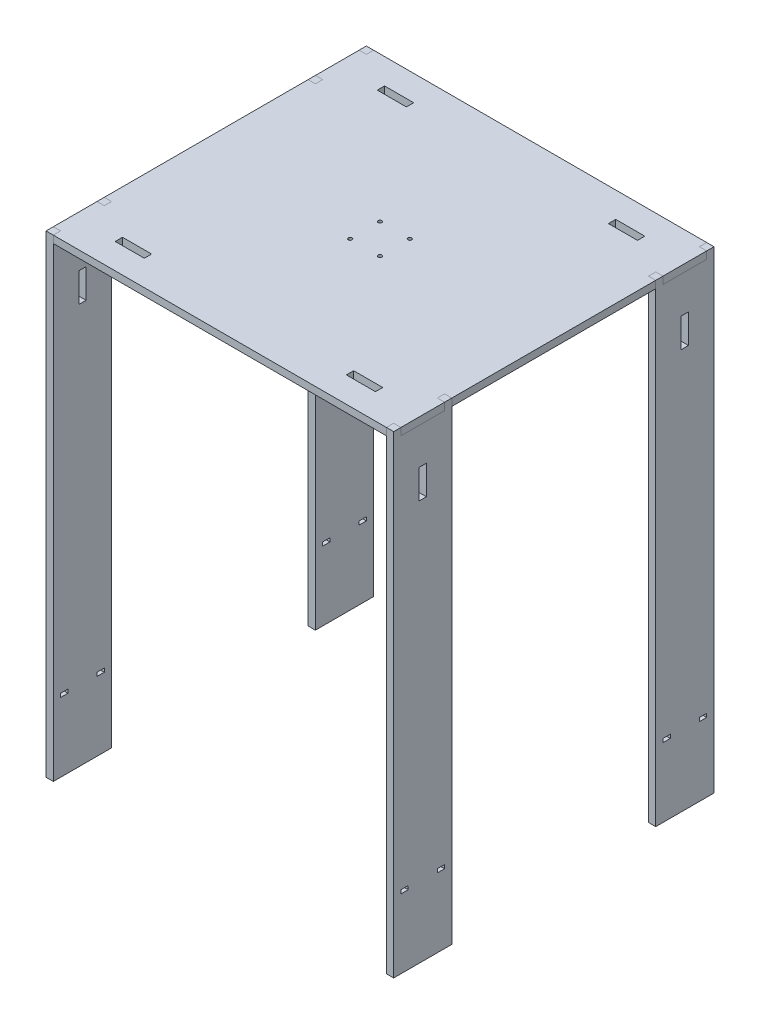
SolidWorks part; units mm, degrees
ref_plane "Front Plane" through (0, 0, 0) normal (0, 0, 1) x (1, 0, 0)
ref_plane "Top Plane" through (0, 0, 0) normal (0, 1, 0) x (1, 0, 0)
ref_plane "Right Plane" through (0, 0, 0) normal (1, 0, 0) x (0, 0, -1)
sketch "Sketch1" plane through (0, 0, 0) normal (0, 1, 0) x (1, 0, 0)
  line L0 (145.2562, 0) -> (-145.2562, 0) construction
  line L1 (-145.2562, 0) -> (-151.6062, 0) construction
  line L2 (0, 0) -> (0, 36.9734) construction
  line L3 (-145.2562, -25.4) -> (-151.6063, -25.4)
  line L4 (-145.2562, -25.4) -> (-145.2562, 25.4)
  line L5 (-145.2562, 25.4) -> (-151.6063, 25.4)
  line L6 (-151.6063, -25.4) -> (-151.6063, 25.4)
  line L7 (-145.2562, -25.4) -> (-151.6063, 25.4) construction
  line L8 (-145.2562, 25.4) -> (-151.6063, -25.4) construction
  line L9 (145.2562, 25.4) -> (151.6063, 25.4)
  line L10 (151.6063, -25.4) -> (151.6063, 25.4)
  line L11 (145.2562, -25.4) -> (151.6063, -25.4)
  line L12 (145.2562, -25.4) -> (145.2562, 25.4)
  point P0 (-148.4313, 0)
  point P4 (0, 0)
  dimension "D1" = 290.5125
  dimension "D2" = 6.35
  dimension "D3" = 50.8
extrude "Boss-Extrude1" add sketch "Sketch1" along normal blind 412.75
sketch "Sketch3" plane through (151.6063, 0, 0) normal (1, 0, 0) x (0, 0, -1)
  line L0 (0, 412.75) -> (0, 409.575) construction
  line L1 (-25.4, 412.75) -> (25.4, 412.75) construction
  line L2 (-25.4, 412.75) -> (-25.4, 0) construction
  line L3 (19.05, 406.4) -> (-19.05, 406.4)
  line L4 (19.05, 406.4) -> (19.05, 412.75)
  line L5 (19.05, 412.75) -> (-19.05, 412.75)
  line L6 (-19.05, 406.4) -> (-19.05, 412.75)
  line L7 (19.05, 406.4) -> (-19.05, 412.75) construction
  line L8 (19.05, 412.75) -> (-19.05, 406.4) construction
  line L9 (0, 406.4) -> (0, 63.5) construction
  line L10 (0, 63.5) -> (-19.05, 63.5) construction
  line L11 (19.05, 60.325) -> (12.7, 60.325)
  line L12 (-19.05, 63.5) -> (-12.7, 63.5)
  line L13 (-19.05, 63.5) -> (-19.05, 60.325)
  line L14 (-19.05, 60.325) -> (-12.7, 60.325)
  line L15 (-12.7, 63.5) -> (-12.7, 60.325)
  line L16 (12.7, 63.5) -> (12.7, 60.325)
  line L17 (19.05, 63.5) -> (12.7, 63.5)
  line L18 (19.05, 63.5) -> (19.05, 60.325)
  dimension "D1" = 3.175
  dimension "D2" = 6.35
  dimension "D3" = 342.9
  dimension "D4" = 6.35
  dimension "D5" = 6.35
  dimension "D6" = 3.175
extrude "Cut-Extrude1" cut sketch "Sketch3" against normal through all
sketch "Sketch4" plane through (0, 412.75, 0) normal (0, 1, 0) x (1, 0, 0)
  line L1 (-145.2562, 19.05) -> (-151.6063, 19.05)
  line L2 (-145.2562, 19.05) -> (-145.2562, -19.05)
  line L3 (-145.2562, -19.05) -> (-151.6063, -19.05)
  line L4 (-151.6063, 19.05) -> (-151.6063, -19.05)
  line L5 (151.6063, 19.05) -> (145.2562, 19.05)
  line L6 (151.6063, 19.05) -> (151.6063, -19.05)
  line L7 (151.6063, -19.05) -> (145.2562, -19.05)
  line L8 (145.2562, 19.05) -> (145.2562, -19.05)
  line L9 (145.2562, 25.4) -> (-145.2562, 25.4)
  line L10 (145.2562, 25.4) -> (145.2562, -25.4)
  line L11 (145.2562, -25.4) -> (-145.2562, -25.4)
  line L12 (-145.2562, 25.4) -> (-145.2562, -25.4)
  line M1 (-151.6063, 19.05) -> (-145.2562, 19.05)
  line M2 (-145.2562, 19.05) -> (-145.2562, 25.4)
extrude "Boss-Extrude2" add sketch "Sketch4" against normal blind 6.35 separate body contours L4 L3 L2 M1 | L2 L12 L11 L10 L8 L9 M2 | L5 L8 L7 L6 region at (-148.4313, 412.75, 0) region at (0, 412.75, 0) region at (148.4313, 412.75, 0)
sketch "Sketch5" plane through (0, 0, 0) normal (0, 1, 0) x (1, 0, 0)
  line L0 (151.6063, 25.4) -> (151.6063, 203.2) construction
  line L1 (151.6063, 114.3) -> (35.7143, 114.3) construction
  dimension "D1" = 177.8
ref_plane "Plane1" through (0, 0, -114.3) normal (0, 0, -1) x (-1, 0, 0)
mirror "Mirror6" about plane through (0, 0, -114.3) normal (0, 0, -1) of bodies 105 104 103
sketch "Sketch8" plane through (0, 412.75, 0) normal (0, 1, 0) x (1, 0, 0)
  line L1 (-151.6063, 203.2) -> (151.6063, 203.2)
  line L2 (-151.6063, 203.2) -> (-151.6063, 25.4)
  line L3 (-151.6063, 25.4) -> (151.6063, 25.4)
  line L4 (151.6063, 203.2) -> (151.6063, 25.4)
extrude "Boss-Extrude5" add sketch "Sketch8" against normal blind 6.35
sketch "Sketch9" plane through (0, 412.75, 0) normal (0, 1, 0) x (1, 0, 0)
  line L0 (-151.6063, 114.3) -> (151.6063, 114.3) construction
  line L1 (-151.6063, 203.2) -> (-151.6063, 25.4) construction
  line L2 (151.6063, 25.4) -> (151.6063, 203.2) construction
  line L3 (0, 254) -> (0, -25.4) construction
  line L4 (145.2562, 254) -> (-145.2562, 254) construction
  line L5 (145.2562, -25.4) -> (-145.2562, -25.4) construction
  line L6 (0, 254) -> (0, 228.6) construction
  line L7 (13, 101.3) -> (-13, 101.3) construction
  line L8 (13, 101.3) -> (13, 127.3) construction
  line L9 (13, 127.3) -> (-13, 127.3) construction
  line L10 (-13, 101.3) -> (-13, 127.3) construction
  line L11 (13, 101.3) -> (-13, 127.3) construction
  line L12 (13, 127.3) -> (-13, 101.3) construction
  line L13 (18.7789, 228.6) -> (-18.7789, 228.6) construction
  point P12 (0, 114.3)
  point P13 (0, 114.3)
  point P19 (-13, 127.3)
  point P20 (13, 127.3)
  point P21 (13, 101.3)
  point P22 (-13, 101.3)
  point P25 (0, 228.6)
  dimension "D1" = 26
  dimension "D2" = 25.4
hole_wizard "M3 Clearance Hole1" positions "Sketch10" profile "Sketch11" hole size "M3" standard "ANSI Metric" end condition through all
sketch "Sketch10" plane through (0, 412.75, 0) normal (0, 1, 0) x (1, 0, 0)
  point P0 (-13, 101.3)
  point P3 (-13, 127.3)
  point P6 (13, 127.3)
  point P9 (13, 101.3)
sketch "Sketch11" plane through (-13, 412.75, -101.3) normal (1, 0, 0) x (0, 0, 1)
  line L0 (0, 0) -> (0, 412.75)
  line L1 (0, 412.75) -> (1.6, 412.75)
  line L2 (1.6, 412.75) -> (1.6, 0)
  line L5 (1.6, 0) -> (0, 0)
  line L11 (0, -6.35) -> (0, 107.95) construction
  dimension "Thru Hole Dia." = 3.2
  dimension "Thru Hole Depth" = 412.75
sketch "Sketch12" plane through (0, 412.75, 0) normal (0, 1, 0) x (1, 0, 0)
  line L0 (-151.6063, 0) -> (-100.8063, 0) construction
  line L1 (-151.6063, 19.05) -> (-151.6063, -19.05) construction
  line L2 (0, -25.4) -> (0, 254) construction
  line L3 (-113.5063, -3.175) -> (-88.1063, -3.175)
  line L4 (-113.5063, -3.175) -> (-113.5063, 3.175)
  line L5 (-113.5063, 3.175) -> (-88.1063, 3.175)
  line L6 (-88.1063, -3.175) -> (-88.1063, 3.175)
  line L7 (-113.5063, -3.175) -> (-88.1063, 3.175) construction
  line L8 (-113.5063, 3.175) -> (-88.1063, -3.175) construction
  line L9 (145.2562, -25.4) -> (-145.2562, -25.4) construction
  line L10 (145.2562, 254) -> (-145.2562, 254) construction
  line L11 (-151.6063, 114.3) -> (151.6063, 114.3) construction
  line L12 (-151.6063, 203.2) -> (-151.6063, 25.4) construction
  line L13 (151.6063, 25.4) -> (151.6063, 203.2) construction
  line L14 (113.5063, 3.175) -> (88.1063, 3.175)
  line L15 (88.1063, -3.175) -> (88.1063, 3.175)
  line L16 (113.5063, -3.175) -> (88.1063, -3.175)
  line L17 (113.5063, -3.175) -> (113.5063, 3.175)
  line L18 (113.5063, 231.775) -> (113.5063, 225.425)
  line L19 (113.5063, 231.775) -> (88.1063, 231.775)
  line L20 (88.1063, 231.775) -> (88.1063, 225.425)
  line L21 (113.5063, 225.425) -> (88.1063, 225.425)
  line L22 (-113.5063, 225.425) -> (-88.1063, 225.425)
  line L23 (-88.1063, 231.775) -> (-88.1063, 225.425)
  line L24 (-113.5063, 231.775) -> (-88.1063, 231.775)
  line L25 (-113.5063, 231.775) -> (-113.5063, 225.425)
  dimension "D1" = 50.8
  dimension "D2" = 6.35
  dimension "D3" = 25.4
extrude "Cut-Extrude2" cut sketch "Sketch12" against normal up to next (6.35 mm away)
sketch "Sketch13" plane through (-151.6063, 0, 0) normal (-1, 0, 0) x (0, 0, 1)
  line L0 (-228.6, 412.75) -> (-228.6, 361.95) construction
  line L1 (-209.55, 412.75) -> (-247.65, 412.75) construction
  line L2 (-114.3, 412.75) -> (-114.3, 406.4)
  line L3 (-225.425, 349.25) -> (-231.775, 349.25)
  line L4 (-225.425, 349.25) -> (-225.425, 374.65)
  line L5 (-225.425, 374.65) -> (-231.775, 374.65)
  line L6 (-231.775, 349.25) -> (-231.775, 374.65)
  line L7 (-225.425, 349.25) -> (-231.775, 374.65) construction
  line L8 (-225.425, 374.65) -> (-231.775, 349.25) construction
  line L9 (-203.2, 412.75) -> (-25.4, 412.75) construction
  line L10 (-203.2, 406.4) -> (-25.4, 406.4) construction
  line L11 (-3.175, 374.65) -> (3.175, 374.65)
  line L12 (3.175, 349.25) -> (3.175, 374.65)
  line L13 (-3.175, 349.25) -> (3.175, 349.25)
  line L14 (-3.175, 349.25) -> (-3.175, 374.65)
  dimension "D1" = 6.35
  dimension "D2" = 25.4
  dimension "D3" = 50.8
extrude "Cut-Extrude3" cut sketch "Sketch13" against normal blind 6.35 contours L6 L3 L4 L5 | L14 L13 L12 L11 region at (-151.6063, 361.95, -228.6) region at (-151.6063, 361.95, 0)
mirror "Mirror7" about plane through (0, 0, 0) normal (1, 0, 0) of "Cut-Extrude3"
